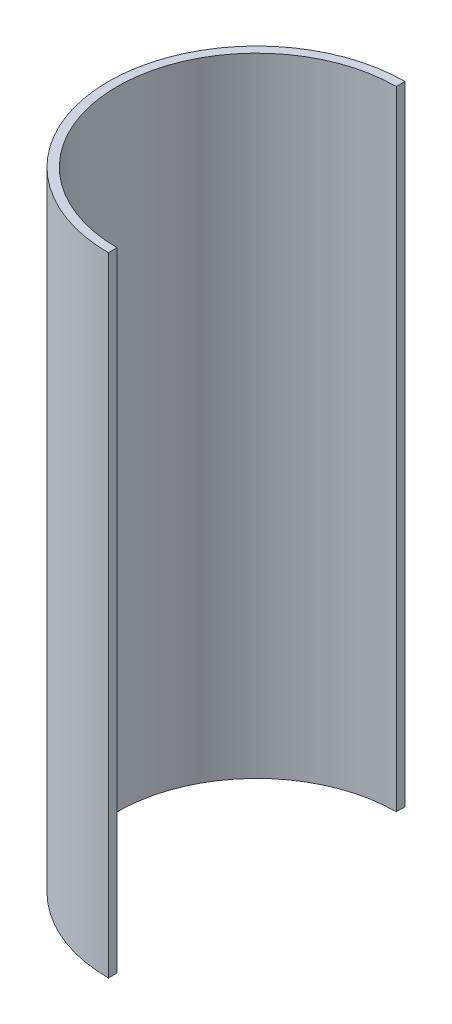
SolidWorks part; units mm, degrees
ref_plane "Front Plane" through (0, 0, 0) normal (0, 0, 1) x (1, 0, 0)
ref_plane "Top Plane" through (0, 0, 0) normal (0, 1, 0) x (1, 0, 0)
ref_plane "Right Plane" through (0, 0, 0) normal (1, 0, 0) x (0, 0, -1)
sketch "Sketch1" plane through (0, 0, 0) normal (0, 1, 0) x (1, 0, 0)
  line L1 (0, 107.95) -> (0, 101.6)
  line L2 (0, -101.6) -> (0, -107.95)
  arc A1 (0, 101.6) -> (0, -101.6) centre (0, 0) ccw
  arc A2 (0, 107.95) -> (0, -107.95) centre (0, 0) ccw
  dimension "D1" = 101.6
  dimension "D2" = 6.35
  dimension "D3" = 107.95
  dimension "D4" = 6.35
extrude "Boss-Extrude1" add sketch "Sketch1" along normal blind 457.2
